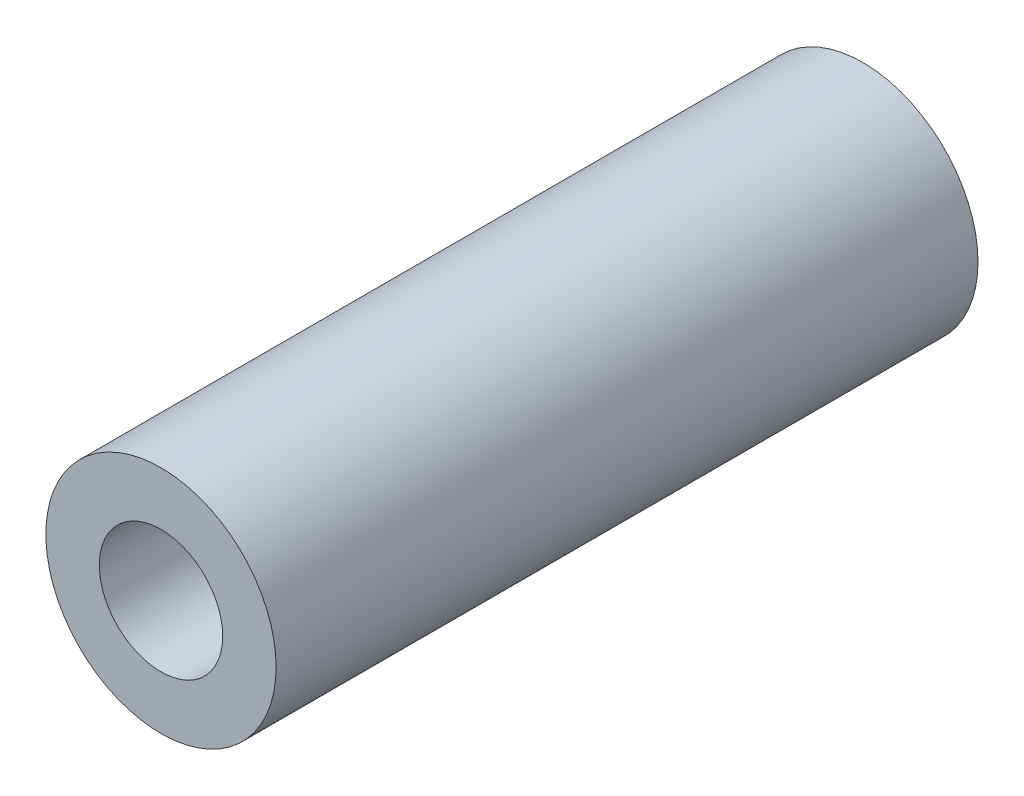
SolidWorks part; units mm, degrees
ref_plane "Front Plane" through (0, 0, 0) normal (0, 0, 1) x (1, 0, 0)
ref_plane "Top Plane" through (0, 0, 0) normal (0, 1, 0) x (1, 0, 0)
ref_plane "Right Plane" through (0, 0, 0) normal (1, 0, 0) x (0, 0, -1)
sketch "Sketch1" plane through (0, 0, 0) normal (0, 0, 1) x (1, 0, 0)
  circle A0 centre (0, 0) radius 4.7625
  circle A1 centre (0, 0) radius 2.5527
  dimension "D1" = 5.1054
  dimension "D2" = 9.525
extrude "Boss-Extrude1" add sketch "Sketch1" along normal mid plane 29.0335 contours A0 A1 region at (-4.6278, 0, 0)
